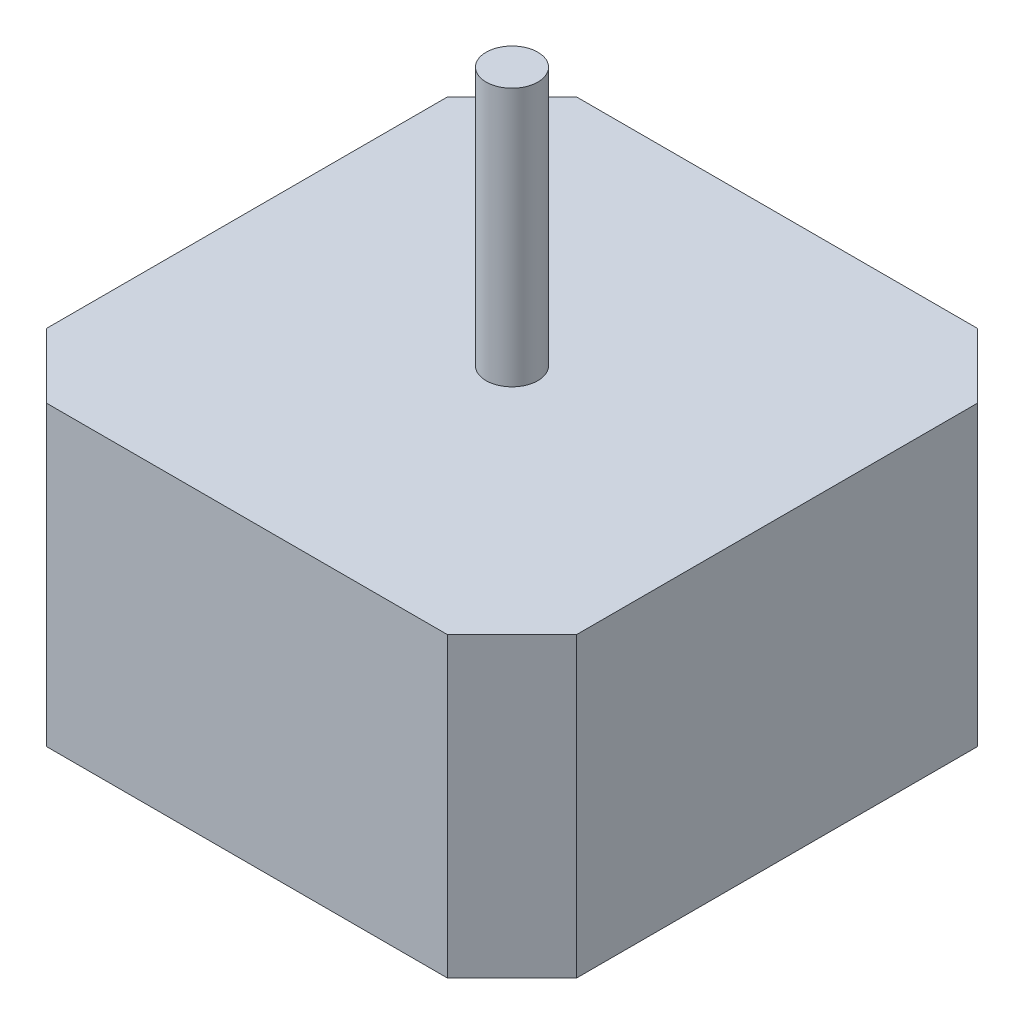
SolidWorks part; units mm, degrees
ref_plane "Front Plane" through (0, 0, 0) normal (0, 0, 1) x (1, 0, 0)
ref_plane "Top Plane" through (0, 0, 0) normal (0, 1, 0) x (1, 0, 0)
ref_plane "Right Plane" through (0, 0, 0) normal (1, 0, 0) x (0, 0, -1)
sketch "Sketch2" plane through (0, 0, 0) normal (0, 1, 0) x (1, 0, 0)
  line L0 (-20.5, 20.5) -> (-7.4847, 20.5) construction
  line L1 (-20.5, 20.5) -> (20.5, 20.5)
  line L2 (-20.5, 20.5) -> (-20.5, -20.5)
  line L3 (-20.5, -20.5) -> (20.5, -20.5)
  line L4 (20.5, 20.5) -> (20.5, -20.5)
  line L5 (0, -20.5) -> (0, 20.5) construction
  line L6 (-20.5, 0) -> (20.5, 0) construction
  line L7 (20.5, 20.5) -> (7.5093, 20.5) construction
  line L8 (7.5093, 20.5) -> (7.5093, 24.5028) construction
  line L9 (7.5093, 24.5028) -> (-7.4847, 24.5028) construction
  line L11 (-7.4847, 20.5) -> (7.5093, 20.5)
  line L12 (-7.4847, 20.5) -> (-7.4847, 24.5028)
  line L13 (-7.4847, 24.5028) -> (7.5093, 24.5028)
  line L14 (7.5093, 20.5) -> (7.5093, 24.5028)
  point P0 (0, 0)
  dimension "D1" = 41
  dimension "D2" = 41
extrude "Boss-Extrude7" add sketch "Sketch2" along normal blind 23 contours L4 L1 L2 L3 | L1 L14 L13 L12 region at (0, 0, 0) region at (0.0123, 0, -22.5014)
sketch "Sketch3" plane through (0, 23, 0) normal (0, 1, 0) x (1, 0, 0)
  circle A0 centre (0, 0) radius 2
sketch "Sketch6" plane through (0, 0, 0) normal (0, 1, 0) x (1, 0, 0)
  line L0 (-20.5, 20.5) -> (-15.5, 20.5)
  line L1 (-20.5, 20.5) -> (-7.4847, 20.5) construction
  line L2 (-20.5, 20.5) -> (-20.5, 15.5)
  line L3 (-20.5, 20.5) -> (-20.5, -20.5) construction
  line L4 (-20.5, 15.5) -> (-15.5, 20.5)
extrude "Cut-Extrude1" cut sketch "Sketch6" along normal blind 23 contours L0 L4 L2
sketch "Sketch7" plane through (0, 0, 0) normal (0, 1, 0) x (1, 0, 0)
  line L0 (-20.5, -20.5) -> (-20.5, -15.5)
  line L1 (-20.5, 15.5) -> (-20.5, -20.5) construction
  line L2 (-20.5, -20.5) -> (-15.5, -20.5)
  line L3 (-20.5, -20.5) -> (20.5, -20.5) construction
  line L4 (-20.5, -15.5) -> (-15.5, -20.5)
  line L5 (20.5, -20.5) -> (15.5, -20.5)
  line L6 (20.5, -20.5) -> (20.5, -15.5)
  line L7 (20.5, 20.5) -> (20.5, -20.5) construction
  line L8 (20.5, -15.5) -> (15.5, -20.5)
  line L9 (20.5, 20.5) -> (20.5, 15.5)
  line L10 (20.5, 20.5) -> (15.5, 20.5)
  line L11 (7.5093, 20.5) -> (20.5, 20.5) construction
  line L12 (15.5, 20.5) -> (20.5, 15.5)
extrude "Cut-Extrude3" cut sketch "Sketch7" along normal blind 23 contours L4 L2 L0 | L8 L5 L6 | L12 L9 L10
sketch "Sketch8" plane through (0, 23, 0) normal (0, 1, 0) x (1, 0, 0)
  line L0 (-7.4847, 20.5) -> (7.5093, 20.5)
  line L1 (7.5093, 20.5) -> (7.5093, 24.5028)
  line L2 (7.5093, 24.5028) -> (-7.4847, 24.5028)
  line L3 (-7.4847, 24.5028) -> (-7.4847, 20.5)
extrude "Cut-Extrude4" cut sketch "Sketch8" against normal blind 14 contours L3 L0 L1 L2
extrude "Boss-Extrude11" add sketch "Sketch3" along normal blind 20 contours A0
